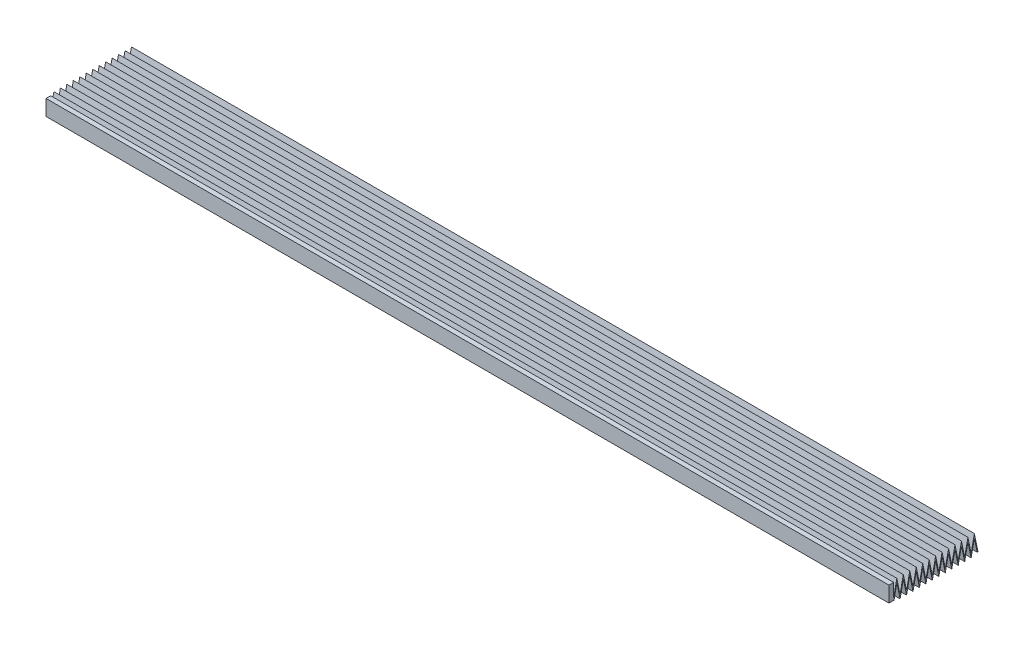
SolidWorks part; units mm, degrees
ref_plane "Front Plane" through (0, 0, 0) normal (0, 0, 1) x (1, 0, 0)
ref_plane "Top Plane" through (0, 0, 0) normal (0, 1, 0) x (1, 0, 0)
ref_plane "Right Plane" through (0, 0, 0) normal (1, 0, 0) x (0, 0, -1)
sketch "Sketch2" plane through (0, 0, 0) normal (0, 0, 1) x (1, 0, 0)
  line L1 (-270, 10) -> (270, 10)
  line L2 (-270, 10) -> (-270, 0)
  line L3 (-270, 0) -> (270, 0)
  line L4 (270, 10) -> (270, 0)
  point P4 (0, 0)
  dimension "D1" = 10
  dimension "D2" = 540
extrude "Boss-Extrude1" add sketch "Sketch2" along normal blind 3
sketch "Sketch3" plane through (270, 0, 0) normal (1, 0, 0) x (0, 0, -1)
  line L0 (0, 10) -> (53.8068, 10) construction
  line L1 (0, 0) -> (53.8068, 0) construction
  line L3 (0, 0) -> (2.0695, 10)
  line L4 (2.0695, 10) -> (4.139, 0)
  line L5 (4.139, 0) -> (6.2085, 10)
  line L6 (6.2085, 10) -> (8.278, 0)
  line L7 (8.278, 0) -> (10.3475, 10)
  line L8 (10.3475, 10) -> (12.4169, 0)
  line L9 (12.4169, 0) -> (14.4864, 10)
  line L10 (14.4864, 10) -> (16.5559, 0)
  line L11 (16.5559, 0) -> (18.6254, 10)
  line L12 (18.6254, 10) -> (20.6949, 0)
  line L13 (20.6949, 0) -> (22.7644, 10)
  line L14 (22.7644, 10) -> (24.8339, 0)
  line L15 (24.8339, 0) -> (26.9034, 10)
  line L16 (26.9034, 10) -> (28.9729, 0)
  line L17 (28.9729, 0) -> (31.0424, 10)
  line L18 (31.0424, 10) -> (33.1119, 0)
  line L20 (33.1119, 0) -> (35.1814, 10)
  line L21 (35.1814, 10) -> (37.2508, 0)
  line L22 (37.2508, 0) -> (39.3203, 10)
  line L23 (39.3203, 10) -> (41.3898, 0)
  line L24 (41.3898, 0) -> (43.4593, 10)
  line L25 (43.4593, 10) -> (45.5288, 0)
  line L26 (45.5288, 0) -> (47.5983, 10)
  line L27 (47.5983, 10) -> (49.6678, 0)
  line L28 (49.6678, 0) -> (51.7373, 10)
  line L29 (51.7373, 10) -> (53.8068, 0)
  line L30 (53.8068, 10) -> (53.8068, 0) construction
  line L32 (53.8068, 10) -> (53.8068, 0) construction
extrude "Extrude-Thin1" add sketch "Sketch3" against normal through all thin thin type mid plane wall 0.5
